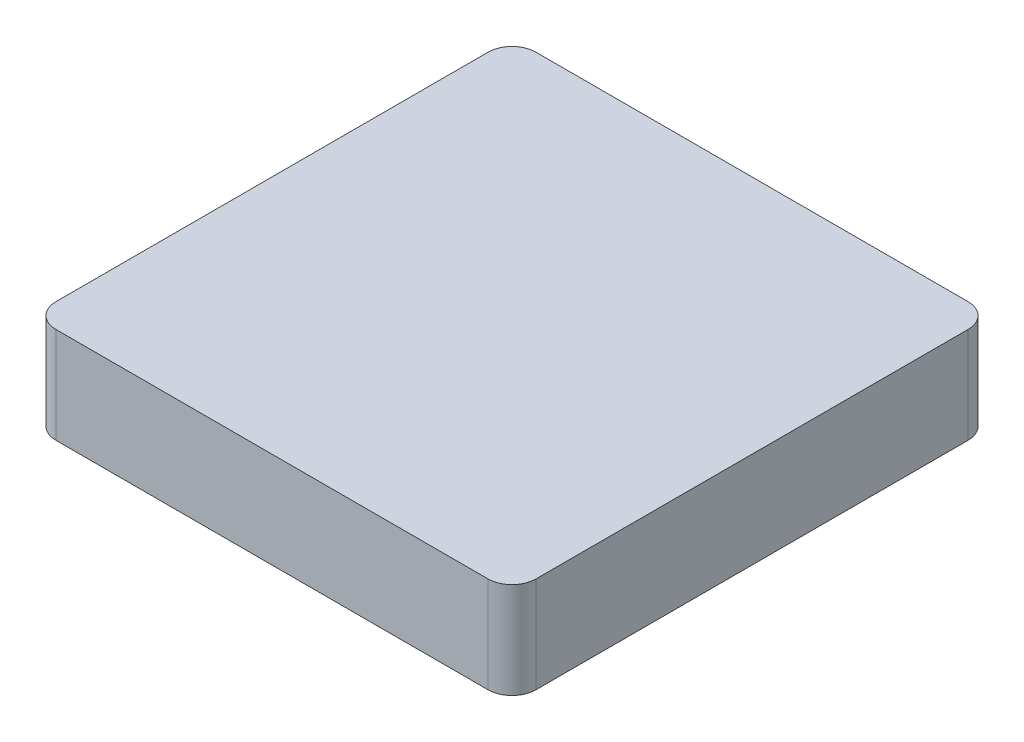
SolidWorks part; units mm, degrees
ref_plane "Front Plane" through (0, 0, 0) normal (0, 0, 1) x (1, 0, 0)
ref_plane "Top Plane" through (0, 0, 0) normal (0, 1, 0) x (1, 0, 0)
ref_plane "Right Plane" through (0, 0, 0) normal (1, 0, 0) x (0, 0, -1)
sketch "Sketch1" plane through (0, 0, 0) normal (0, 1, 0) x (1, 0, 0)
  line L0 (0, 0) -> (12.7, 0)
  line L1 (12.7, 0) -> (12.7, 12.7)
  line L2 (12.7, 12.7) -> (0, 12.7)
  line L3 (0, 12.7) -> (0, 0)
  dimension "D1" = 12.7
  dimension "D2" = 12.7
extrude "Boss-Extrude1" add sketch "Sketch1" along normal blind 2.54
fillet "Fillet1" radius 0.635 4 edges at (0, 1.27, -12.7) (12.7, 1.27, -12.7) (12.7, 1.27, 0) (0, 1.27, 0)
shell "Shell1" thickness 0.635 removed face at (6.35, 0, -6.35)
sketch "Sketch2" plane through (0, 1.905, 0) normal (0, -1, 0) x (-1, 0, 0)
  line L0 (-0.635, 6.35) -> (-12.065, 6.35) construction
  line L1 (-0.635, 12.065) -> (-0.635, 0.635) construction
  line L2 (-12.065, 0.635) -> (-12.065, 12.065) construction
  line L3 (-6.35, 0.635) -> (-6.35, 12.065) construction
  line L4 (-0.635, 0.635) -> (-12.065, 0.635) construction
  line L5 (-12.065, 12.065) -> (-0.635, 12.065) construction
  circle A0 centre (-6.35, 6.35) radius 2.54
  dimension "D1" = 5.08
extrude "Boss-Extrude2" add sketch "Sketch2" along normal up to surface (1.905 mm away) up to face at (6.35, 0, -6.35)
